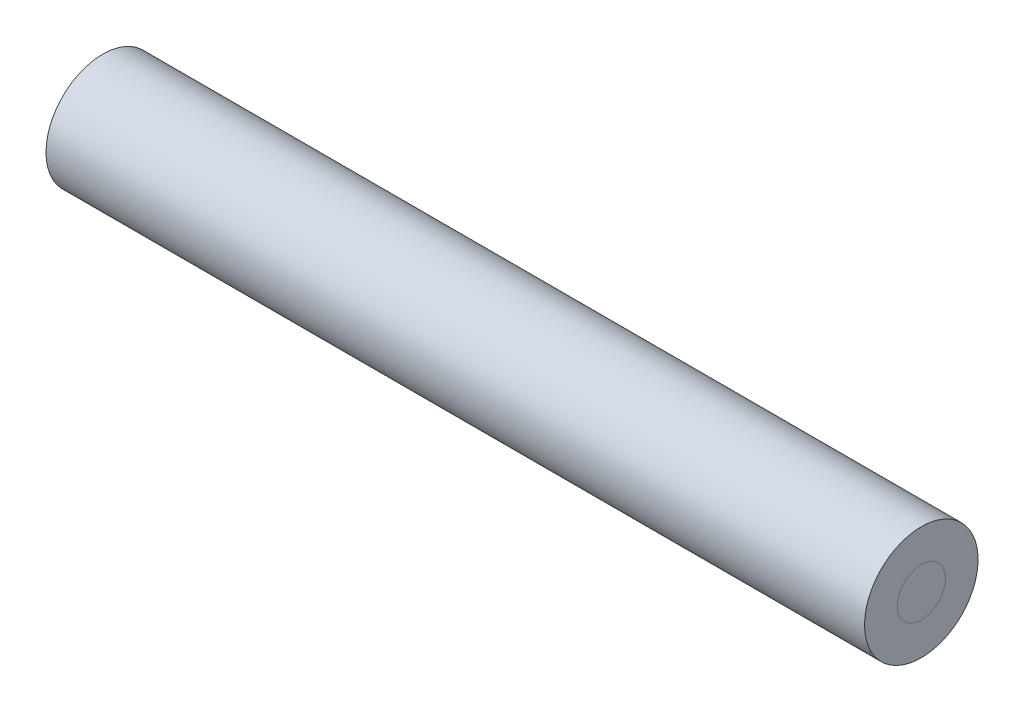
SolidWorks part; units mm, degrees
ref_plane "Front Plane" through (0, 0, 0) normal (0, 0, 1) x (1, 0, 0)
ref_plane "Top Plane" through (0, 0, 0) normal (0, 1, 0) x (1, 0, 0)
ref_plane "Right Plane" through (0, 0, 0) normal (1, 0, 0) x (0, 0, -1)
other "Configuration Table"
sketch "Sketch1" plane through (-3.3146, 0, 0) normal (-1, 0, 0) x (0, 0, 1)
  circle A0 centre (-16.7706, 50.6058) radius 1.4097
  circle A1 centre (-16.7706, 50.6058) radius 0.5969
  point P2 (0, 0)
  dimension "D1" = 2.8194
  dimension "D2" = 1.1938
extrude "Boss-Extrude1" add sketch "Sketch1" along normal blind 20.32 contours A1 region at (-3.3146, 50.6058, -16.7706)
extrude "Boss-Extrude2" add sketch "Sketch1<3>" along normal blind 20.32 separate body contours A0 A1 region at (-3.3146, 50.6058, -18.1405)
sketch "Sketch1<3>" plane through (-3.3146, 0, 0) normal (-1, 0, 0) x (0, 0, 1) same geometry as "Sketch1"
